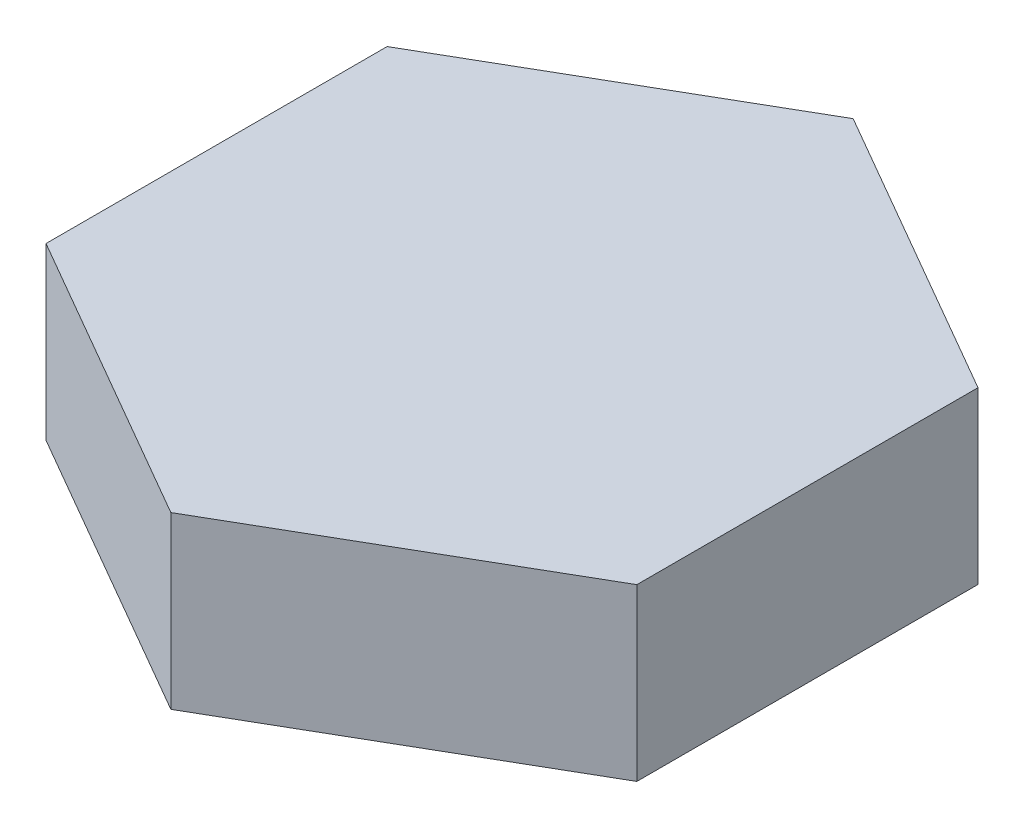
SolidWorks part; units mm, degrees
ref_plane "Front Plane" through (0, 0, 0) normal (0, 0, 1) x (1, 0, 0)
ref_plane "Top Plane" through (0, 0, 0) normal (0, 1, 0) x (1, 0, 0)
ref_plane "Right Plane" through (0, 0, 0) normal (1, 0, 0) x (0, 0, -1)
sketch "Sketch1" plane through (0, 0, 0) normal (0, 1, 0) x (1, 0, 0)
  line L1 (0, 270.1999) -> (-234, 135.1)
  line L2 (-234, 135.1) -> (-234, -135.1)
  line L3 (-234, -135.1) -> (0, -270.1999)
  line L4 (0, -270.1999) -> (234, -135.1)
  line L5 (234, -135.1) -> (234, 135.1)
  line L6 (234, 135.1) -> (0, 270.1999)
  circle A0 centre (0, 0) radius 234 construction
  dimension "D1" = 468
extrude "Boss-Extrude1" add sketch "Sketch1" along normal blind 135
